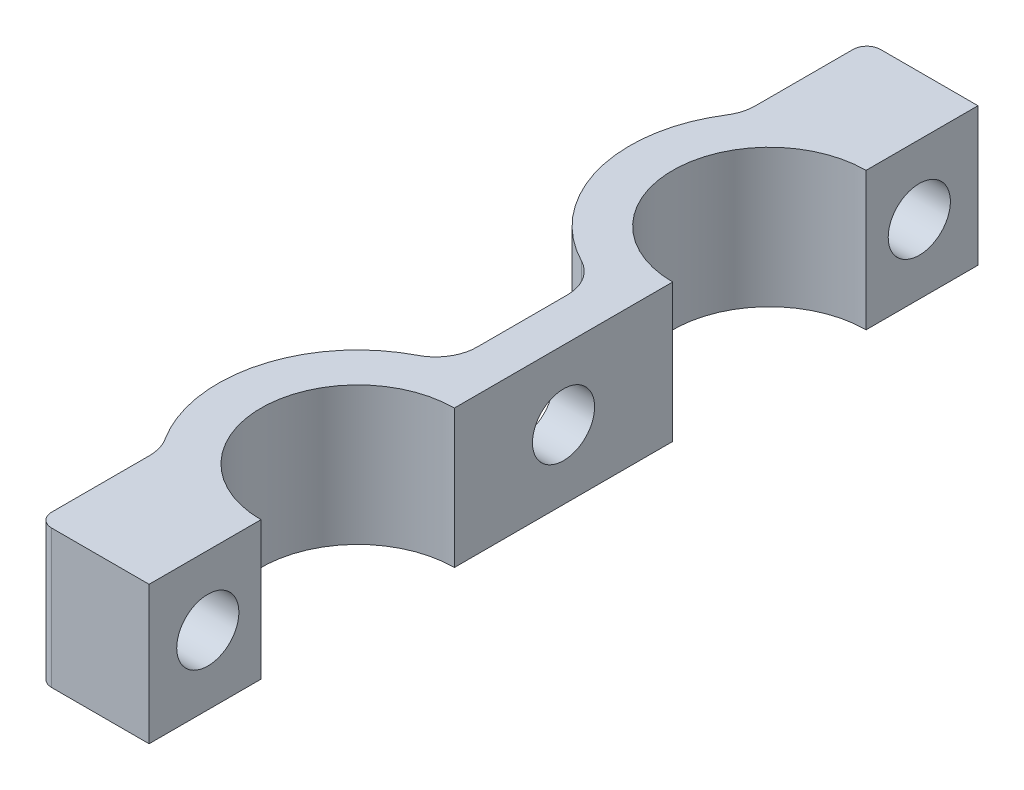
SolidWorks part; units mm, degrees
material "3.1355 (EN-AW 2024)"
ref_plane "Front" through (0, 0, 0) normal (0, 0, 1) x (1, 0, 0)
ref_plane "Top" through (0, 0, 0) normal (0, 1, 0) x (1, 0, 0)
ref_plane "Right" through (0, 0, 0) normal (1, 0, 0) x (0, 0, -1)
sketch "Эскиз1" plane through (0, 0, 0) normal (0, 1, 0) x (1, 0, 0)
  line L0 (0, 0) -> (0, 60) construction
  line L1 (0, 30) -> (-15.0292, 30) construction
  line L2 (0, 0) -> (0, 8)
  line L3 (0, 60) -> (0, 52)
  line L4 (0, 37.8) -> (0, 22.2)
  line L5 (-3, 0) -> (-3, 5.4558)
  line L6 (-3, 35.2558) -> (-3, 24.7442)
  line L7 (-3, 60) -> (-3, 54.5442)
  line L8 (-3, 60) -> (0, 60)
  line L9 (-3, 0) -> (0, 0)
  circle A0 centre (0, 15.1) radius 7.1 construction
  circle A1 centre (0, 44.9) radius 7.1 construction
  arc A2 (0, 8) -> (0, 22.2) centre (0, 15.1) cw
  arc A3 (0, 52) -> (0, 37.8) centre (0, 44.9) ccw
  arc A4 (-3, 5.4558) -> (-3, 24.7442) centre (0, 15.1) cw
  arc A5 (-3, 54.5442) -> (-3, 35.2558) centre (0, 44.9) ccw
  point P9 (0, 22.2)
  dimension "D2" = 15.1
  dimension "D3" = 14.2
  dimension "D1" = 60
  dimension "D4" = 3
extrude "Бобышка-Вытянуть1" add sketch "Эскиз1" along normal blind 10
sketch "Эскиз2" plane through (0, 10, 0) normal (0, 1, 0) x (1, 0, 0)
  line L0 (-3, 60) -> (-8.0498, 60)
  line L1 (-8.0498, 60) -> (-8.0498, 51)
  line L2 (-3, 60) -> (-3, 54.5442)
  line L3 (0, 30) -> (-3, 30) construction
  line L4 (0, 22.2) -> (0, 37.8) construction
  line L5 (-3, 35.2558) -> (-3, 24.7442) construction
  line L6 (-3, 0) -> (-3, 5.4558)
  line L7 (-8.0498, 0) -> (-8.0498, 9)
  line L8 (-3, 0) -> (-8.0498, 0)
  arc A0 (-3, 54.5442) -> (-3, 35.2558) centre (0, 44.9) ccw construction
  arc A1 (-3, 54.5442) -> (-8.0498, 51) centre (0, 44.9) ccw
  arc A2 (-3, 5.4558) -> (-8.0498, 9) centre (0, 15.1) cw
  dimension "D1" = 9
sketch "Эскиз3" plane through (-3, 0, 0) normal (-1, 0, 0) x (0, 0, 1)
  line L0 (-60, 5) -> (-54.7288, 5) construction
  line L1 (-60, 10) -> (-60, 0) construction
  line L3 (-30, 10) -> (-30, 0) construction
  line L4 (-35.2558, 10) -> (-24.7442, 10) construction
  line L5 (-35.2558, 0) -> (-24.7442, 0) construction
  circle A0 centre (-55.75, 5) radius 2.25
  circle A1 centre (-4.25, 5) radius 2.25
  point P6 (-58, 5)
  point P7 (-53.5, 5)
  dimension "D1" = 4.5
  dimension "D2" = 2
extrude "Бобышка-Вытянуть2" add sketch "Эскиз2" against normal up to surface (10 mm away) up to face at (-3.8667, 0, -30)
extrude "Вырез-Вытянуть1" cut sketch "Эскиз3" against normal through all and the other way up to surface (5.0498 mm away) other way up to face at (-8.0498, 5, -55.5)
sketch "Эскиз4" plane through (-3, 0, 0) normal (-1, 0, 0) x (0, 0, 1)
  line L0 (-30, 10) -> (-30, 0) construction
  line L1 (-35.2558, 10) -> (-24.7442, 10) construction
  line L2 (-35.2558, 0) -> (-24.7442, 0) construction
  circle A0 centre (-30, 5) radius 2.25
  dimension "D1" = 4.5
extrude "Вырез-Вытянуть2" cut sketch "Эскиз4" against normal through all
fillet "Скругление1" radius 3 4 edges at (-8.0498, 5, -9) (-8.0498, 5, -51) (-3, 5, -35.2558) (-3, 5, -24.7442)
fillet "Скругление2" radius 1 2 edges at (-8.0498, 5, -60) (-8.0498, 5, 0)
sketch "Эскиз5" plane through (0, 0, 0) normal (0, -1, 0) x (1, 0, 0)
  line L0 (0, -8) -> (0, -8.1)
  line L1 (0, -51.9) -> (0, -52)
  line L2 (0, -37.8) -> (0, -37.9)
  line L3 (0, -22.1) -> (0, -22.2)
  arc A0 (0, -8) -> (0, -22.2) centre (0, -15.1) ccw construction
  arc A1 (0, -37.8) -> (0, -52) centre (0, -44.9) ccw construction
  arc A2 (0, -8) -> (0, -22.2) centre (0, -15.1) ccw
  arc A3 (0, -37.8) -> (0, -52) centre (0, -44.9) ccw
  arc A4 (0, -8.1) -> (0, -22.1) centre (0, -15.1) ccw
  arc A5 (0, -37.9) -> (0, -51.9) centre (0, -44.9) ccw
  dimension "D1" = 0.1
extrude "Бобышка-Вытянуть3" add sketch "Эскиз5" against normal through all
sketch "Эскиз6" plane through (0, 0, 0) normal (0, -1, 0) x (1, 0, 0)
  line L0 (-10.1, -44.9) -> (-10.1, -60) construction
  line L1 (-7.0498, -60) -> (-10.1, -60) construction
  arc A0 (-4.626, -35.9217) -> (-8.5193, -50.325) centre (0, -44.9) ccw construction
equation "\"D2@Эскиз1\"=8+\"D3@Эскиз1\"/2"
